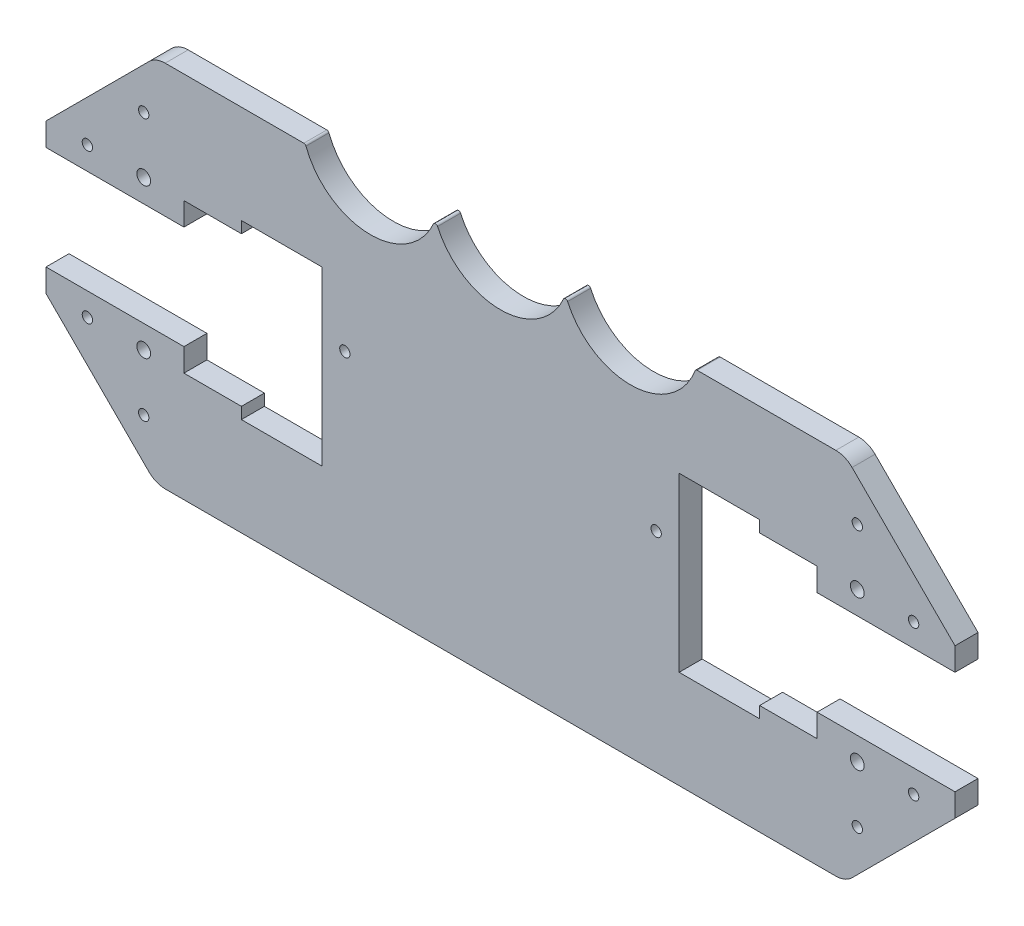
SolidWorks part; units mm, degrees
ref_plane "Plan de face" through (0, 0, 0) normal (0, 0, 1) x (1, 0, 0)
ref_plane "Plan de dessus" through (0, 0, 0) normal (0, 1, 0) x (1, 0, 0)
ref_plane "Plan de droite" through (0, 0, 0) normal (1, 0, 0) x (0, 0, -1)
sketch "Esquisse3" plane through (0, 0, 0) normal (0, 0, 1) x (1, 0, 0)
  line L0 (-197.7, 32.5) -> (-150, 80.2)
  line L1 (-197.7, 32.5) -> (197.7, 32.5)
  line L2 (-197.7, 32.5) -> (-197.7, -32.5)
  line L3 (-197.7, -32.5) -> (197.7, -32.5)
  line L4 (197.7, 32.5) -> (197.7, -32.5)
  line L5 (-150, 80.2) -> (150, 80.2)
  line L6 (-150, 80.2) -> (-150, 32.5)
  line L7 (-150, 32.5) -> (150, 32.5)
  line L8 (150, 80.2) -> (150, 32.5)
  line L9 (-150, -80.2) -> (150, -80.2)
  line L10 (-150, -80.2) -> (-150, -32.5)
  line L11 (-150, -32.5) -> (150, -32.5)
  line L12 (150, -80.2) -> (150, -32.5)
  line L13 (150, 80.2) -> (197.7, 32.5)
  line L14 (197.7, -32.5) -> (150, -80.2)
  line L15 (-150, -80.2) -> (-197.7, -32.5)
  dimension "D1" = 65
  dimension "D2" = 300
  dimension "D3" = 300
  dimension "D4" = 47.7
  dimension "D5" = 0
  dimension "D6" = 47.7
  dimension "D7" = 47.7
  dimension "D8" = 47.7
  dimension "D9" = 150
  dimension "D10" = 32.5
extrude "Boss.-Extru.1" add sketch "Esquisse3" along normal blind 10 contours L4 L1 L2 L3 | L8 L5 L6 L1 | L9 L12 L3 L10 | L6 L0 L1 | L15 L10 L3 | L14 L3 L12 | L13 L8 L1 region at (-165.9, 48.4, 0) region at (0, 0, 0) region at (0, 56.35, 0) region at (-165.9, -48.4, 0) region at (165.9, 48.4, 0) region at (0, -56.35, 0) region at (165.9, -48.4, 0)
sketch "Esquisse4" plane through (0, 0, 10) normal (0, 0, 1) x (1, 0, 0)
  line L1 (-197.7, 32.5) -> (-112.7, 32.5)
  line L2 (-197.7, 32.5) -> (-197.7, -32.5)
  line L3 (-197.7, -32.5) -> (-112.7, -32.5)
  line L4 (-112.7, 32.5) -> (-112.7, -32.5)
  line L5 (-112.7, -37.5) -> (-77.7, -37.5)
  line L6 (-112.7, -37.5) -> (-112.7, 37.5)
  line L7 (-112.7, 37.5) -> (-77.7, 37.5)
  line L8 (-77.7, -37.5) -> (-77.7, 37.5)
  line L9 (197.7, 32.5) -> (112.7, 32.5)
  line L10 (197.7, 32.5) -> (197.7, -32.5)
  line L11 (197.7, -32.5) -> (112.7, -32.5)
  line L12 (112.7, 32.5) -> (112.7, -32.5)
  line L13 (112.7, 37.5) -> (77.7, 37.5)
  line L14 (112.7, 37.5) -> (112.7, -37.5)
  line L15 (112.7, -37.5) -> (77.7, -37.5)
  line L16 (77.7, 37.5) -> (77.7, -37.5)
  line L17 (-197.7, 32.5) -> (-137.7, 32.5)
  line L18 (-197.7, 32.5) -> (-197.7, 22.5)
  line L19 (-197.7, 22.5) -> (-137.7, 22.5)
  line L20 (-137.7, 32.5) -> (-137.7, 22.5)
  line L21 (-197.7, -32.5) -> (-137.7, -32.5)
  line L22 (-197.7, -32.5) -> (-197.7, -22.5)
  line L23 (-197.7, -22.5) -> (-137.7, -22.5)
  line L24 (-137.7, -32.5) -> (-137.7, -22.5)
  line L25 (197.7, 32.5) -> (137.7, 32.5)
  line L26 (197.7, 32.5) -> (197.7, 22.5)
  line L27 (197.7, 22.5) -> (137.7, 22.5)
  line L28 (137.7, 32.5) -> (137.7, 22.5)
  line L29 (197.7, -32.5) -> (137.7, -32.5)
  line L30 (197.7, -32.5) -> (197.7, -22.5)
  line L31 (197.7, -22.5) -> (137.7, -22.5)
  line L32 (137.7, -32.5) -> (137.7, -22.5)
  line M16 (197.7, -32.5) -> (197.7, 32.5)
  line M20 (-197.7, 32.5) -> (-197.7, -32.5)
  dimension "D1" = 85
  dimension "D2" = 5
  dimension "D3" = 5
  dimension "D4" = 35
  dimension "D5" = 85
  dimension "D6" = 85
  dimension "D7" = 35
  dimension "D8" = 85
  dimension "D9" = 5
  dimension "D10" = 5
  dimension "D11" = 0
  dimension "D12" = 60
  dimension "D13" = 10
  dimension "D14" = 10
  dimension "D15" = 0
  dimension "D16" = 10
  dimension "D17" = 10
  dimension "D18" = 60
extrude "Enlèv. mat.-Extru.1" cut sketch "Esquisse4" against normal blind 10 contours L4 L1 L3 M20 | L5 L8 L7 L6 L4 | L13 L16 L15 L14 L12 | L9 L12 L11 M16 region at (-151.7318, 0, 10) region at (-95.2, 0, 10) region at (151.7318, 0, 10) region at (95.2, 0, 10)
sketch "Esquisse5" plane through (0, 0, 10) normal (0, 0, 1) x (1, 0, 0)
  line L1 (-150, 80.2) -> (150, 80.2) construction
  arc A0 (28.2843, 80.2) -> (-28.2843, 80.2) centre (0, 90.2) cw
  arc A1 (-28.2843, 80.2) -> (-84.8528, 80.2) centre (-56.5685, 90.2) cw
  arc A2 (28.2843, 80.2) -> (84.8528, 80.2) centre (56.5685, 90.2) ccw
  point P6 (0, 80.2)
  dimension "D1" = 10
  dimension "D2" = 30
  dimension "D3" = 30
  dimension "D6" = 30
  dimension "D4" = 10
  dimension "D5" = 10
extrude "Enlèv. mat.-Extru.2" cut sketch "Esquisse5" against normal blind 10 and the other way through all
sketch "Esquisse11" plane through (0, 0, 10) normal (0, 0, 1) x (1, 0, 0)
  line L1 (-165.2, 42.5) -> (-145.2, 42.5)
  line L2 (-165.2, 42.5) -> (-165.2, 22.5)
  line L3 (-165.2, 22.5) -> (-145.2, 22.5)
  line L4 (-145.2, 42.5) -> (-145.2, 22.5)
  line L5 (-77.7, -37.5) -> (-77.7, 37.5) construction
  line L7 (-165.2, -22.5) -> (-145.2, -22.5)
  line L8 (-165.2, -22.5) -> (-165.2, -42.5)
  line L9 (-165.2, -42.5) -> (-145.2, -42.5)
  line L10 (-145.2, -22.5) -> (-145.2, -42.5)
  line L11 (197.7, 22.5) -> (137.7, 22.5) construction
  line L12 (145.2, 42.5) -> (165.2, 42.5)
  line L13 (145.2, 42.5) -> (145.2, 22.5)
  line L14 (145.2, 22.5) -> (165.2, 22.5)
  line L15 (165.2, 42.5) -> (165.2, 22.5)
  line L16 (145.2, -22.5) -> (165.2, -22.5)
  line L17 (145.2, -22.5) -> (145.2, -42.5)
  line L18 (145.2, -42.5) -> (165.2, -42.5)
  line L19 (165.2, -22.5) -> (165.2, -42.5)
  line L21 (77.7, 37.5) -> (77.7, -37.5) construction
  line L23 (197.7, -22.5) -> (137.7, -22.5) construction
  line L24 (-197.7, -22.5) -> (-137.7, -22.5) construction
  line L25 (-197.7, 22.5) -> (-137.7, 22.5) construction
  point P24 (155.2, 22.5)
  dimension "D1" = 20
  dimension "D2" = 20
  dimension "D3" = 0
  dimension "D4" = 67.5
  dimension "D5" = 20
  dimension "D6" = 20
  dimension "D7" = 0
  dimension "D8" = 67.5
  dimension "D9" = 20
  dimension "D10" = 20
  dimension "D11" = 20
  dimension "D12" = 20
  dimension "D13" = 0
  dimension "D14" = 67.5
  dimension "D15" = 67.5
  dimension "D16" = 0
sketch "Esquisse10" plane through (0, 0, 10) normal (0, 0, 1) x (1, 0, 0)
  line L0 (-165.2, 42.5) -> (-165.2, 22.5) construction
  line L1 (-165.2, 42.5) -> (-145.2, 42.5) construction
  line L3 (-165.2, 22.5) -> (-145.2, 22.5) construction
  line L4 (-145.2, 42.5) -> (-145.2, 22.5) construction
  line L5 (-165.2, -22.5) -> (-165.2, -42.5) construction
  line L6 (-165.2, -22.5) -> (-145.2, -22.5) construction
  line L7 (-165.2, -42.5) -> (-145.2, -42.5) construction
  line L8 (145.2, 42.5) -> (165.2, 42.5) construction
  line L9 (165.2, 42.5) -> (165.2, 22.5) construction
  line L10 (145.2, 42.5) -> (145.2, 22.5) construction
  line L11 (165.2, -22.5) -> (165.2, -42.5) construction
  line L12 (145.2, -22.5) -> (165.2, -22.5) construction
  line L13 (145.2, -42.5) -> (165.2, -42.5) construction
  line L14 (145.2, -22.5) -> (145.2, -42.5) construction
  circle A0 centre (-155.2, 57) radius 2.25
  circle A1 centre (-179.7, 32.5) radius 2.25
  circle A2 centre (-155.2, 32.5) radius 3
  circle A3 centre (-155.2, -32.5) radius 3
  circle A4 centre (-179.7, -32.5) radius 2.25
  circle A5 centre (-155.2, -57) radius 2.25
  circle A6 centre (155.2, 32.5) radius 3
  circle A7 centre (155.2, 57) radius 2.25
  circle A8 centre (179.7, 32.5) radius 2.25
  circle A9 centre (155.2, -32.5) radius 3
  circle A10 centre (179.7, -32.5) radius 2.25
  circle A11 centre (155.2, -57) radius 2.25
  dimension "D1" = 4.5
  dimension "D4" = 4.5
  dimension "D9" = 6
  dimension "D10" = 6
  dimension "D17" = 6
  dimension "D18" = 4.5
  dimension "D19" = 4.5
  dimension "D24" = 4.5
  dimension "D25" = 4.5
  dimension "D28" = 6
  dimension "D35" = 4.5
  dimension "D36" = 4.5
  dimension "D2" = 10
  dimension "D3" = 14.5
  dimension "D5" = 14.5
  dimension "D6" = 10
  dimension "D7" = 10
  dimension "D8" = 10
  dimension "D11" = 10
  dimension "D12" = 10
  dimension "D13" = 14.5
  dimension "D14" = 10
  dimension "D15" = 14.5
  dimension "D16" = 10
  dimension "D20" = 14.5
  dimension "D21" = 14.5
  dimension "D22" = 10
  dimension "D23" = 10
  dimension "D26" = 10
  dimension "D27" = 10
  dimension "D29" = 10
  dimension "D30" = 10
  dimension "D31" = 14.5
  dimension "D32" = 14.5
  dimension "D33" = 10
  dimension "D34" = 10
extrude "Enlèv. mat.-Extru.3" cut sketch "Esquisse10" against normal blind 10
sketch "Esquisse13" plane through (0, 0, 10) normal (0, 0, 1) x (1, 0, 0)
  line L0 (-77.7, -37.5) -> (-77.7, 37.5) construction
  line L1 (-77.5, 35.2) -> (77.5, 35.2)
  line L2 (-77.5, 35.2) -> (-77.5, 25.2)
  line L3 (-77.5, 25.2) -> (77.5, 25.2)
  line L4 (77.5, 35.2) -> (77.5, 25.2)
  line L5 (77.7, 37.5) -> (77.7, -37.5) construction
  line L6 (84.8528, 80.2) -> (150, 80.2) construction
  dimension "D1" = 0.2
  dimension "D2" = 0.2
  dimension "D3" = 10
  dimension "D4" = 45
sketch "Esquisse15" plane through (0, 0, 10) normal (0, 0, 1) x (1, 0, 0)
  line L0 (-77.5, 25.2) -> (77.5, 25.2) construction
  line L1 (-77.7, -37.5) -> (-77.7, 37.5) construction
  line L2 (77.7, 37.5) -> (77.7, -37.5) construction
  circle A0 centre (-67.7, 10.7) radius 2.25
  circle A1 centre (67.7, 10.7) radius 2.25
  dimension "D1" = 4.5
  dimension "D2" = 4.5
  dimension "D3" = 14.5
  dimension "D4" = 14.5
  dimension "D5" = 10
  dimension "D6" = 10
extrude "Enlèv. mat.-Extru.4" cut sketch "Esquisse15" against normal blind 10
fillet "Congé1" radius 10 4 edges at (150, 80.2, 5) (150, -80.2, 5) (-150, 80.2, 5) (-150, -80.2, 5)
fillet "Congé3" radius 1 4 edges at (-84.8528, 80.2, 5) (-28.2843, 80.2, 5) (28.2843, 80.2, 5) (84.8528, 80.2, 5)
